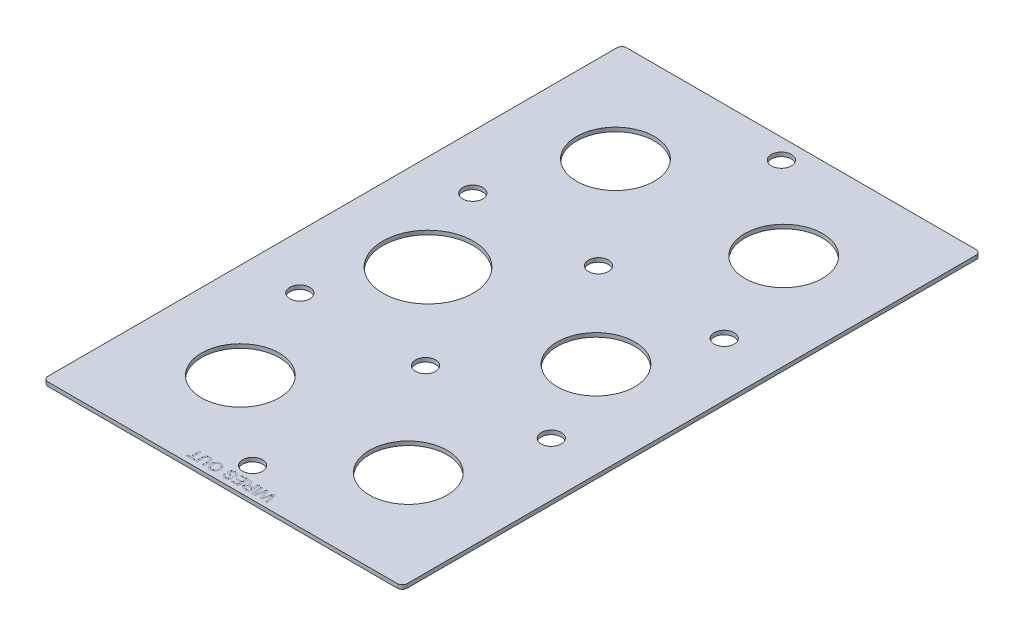
SolidWorks part; units mm, degrees
ref_plane "Front" through (0, 0, 0) normal (0, 0, 1) x (1, 0, 0)
ref_plane "Top" through (0, 0, 0) normal (0, 1, 0) x (1, 0, 0)
ref_plane "Right" through (0, 0, 0) normal (1, 0, 0) x (0, 0, -1)
sketch "Sketch1" plane through (0, 0, 0) normal (0, 1, 0) x (1, 0, 0)
  line L0 (-78.1178, -119.38) -> (-78.2448, -119.38) construction
  line L1 (-111.125, 184.15) -> (111.125, 184.15)
  line L2 (-114.3, 180.975) -> (-114.3, -180.975)
  line L3 (-111.125, -184.15) -> (111.125, -184.15)
  line L4 (114.3, 180.975) -> (114.3, -180.975)
  line L5 (-114.3, 184.15) -> (114.3, -184.15) construction
  line L6 (-114.3, -184.15) -> (114.3, 184.15) construction
  line L7 (-73.1137, 20.0643) -> (-33.9219, -19.9357) construction
  circle A0 centre (53.5178, -119.5086) radius 24.727
  circle A1 centre (53.5178, -0.0643) radius 24.727
  circle A2 centre (-53.5178, -119.38) radius 24.727
  circle A4 centre (-53.5178, 119.38) radius 24.727
  circle A5 centre (53.5178, 119.38) radius 24.727
  arc A6 (-29.1293, -122.5989) -> (-75.7712, -108.8944) centre (-53.5178, -119.38) ccw construction
  arc A7 (-29.1293, -122.5989) -> (-77.9063, -116.1611) centre (-53.5178, -119.38) ccw construction
  arc A8 (114.3, 180.975) -> (111.125, 184.15) centre (111.125, 180.975) ccw
  arc A9 (-114.3, 180.975) -> (-111.125, 184.15) centre (-111.125, 180.975) cw
  arc A10 (-114.3, -180.975) -> (-111.125, -184.15) centre (-111.125, -180.975) ccw
  arc A11 (111.125, -184.15) -> (114.3, -180.975) centre (111.125, -180.975) ccw
  circle A12 centre (-53.5178, 0.0643) radius 28.7693
  circle A13 centre (-80.01, -55.0291) radius 2.2479 construction
  circle A14 centre (-80.01, -55.0291) radius 2.2479 construction
  circle A15 centre (0, -55.0333) radius 2.2479 construction
  circle A16 centre (0, -55.0333) radius 2.2479 construction
  circle A17 centre (80.01, -55.0291) radius 2.2479 construction
  circle A18 centre (80.01, -55.0291) radius 2.2479 construction
  circle A19 centre (80.01, 55.0291) radius 2.2479 construction
  circle A20 centre (80.01, 55.0291) radius 2.2479 construction
  circle A21 centre (0, 55.0333) radius 2.2479 construction
  circle A22 centre (0, 55.0333) radius 2.2479 construction
  circle A23 centre (-80.01, 55.0291) radius 2.2479 construction
  circle A24 centre (-80.01, 55.0291) radius 2.2479 construction
  circle A25 centre (0, 171.45) radius 2.2479 construction
  circle A26 centre (0, 171.45) radius 2.2479 construction
  circle A27 centre (0, -165.1) radius 2.2479 construction
  circle A28 centre (0, -165.1) radius 2.2479 construction
  circle A29 centre (0, -165.1) radius 6.35
  circle A30 centre (80.01, -55.0291) radius 6.35
  circle A31 centre (0, -55.0333) radius 6.35
  circle A32 centre (-80.01, -55.0291) radius 6.35
  circle A33 centre (80.01, 55.0291) radius 6.35
  circle A34 centre (0, 55.0333) radius 6.35
  circle A35 centre (-80.01, 55.0291) radius 6.35
  circle A36 centre (0, 171.45) radius 6.35
  point P0 (0, 0)
  dimension "D3" = 0.127
  dimension "D4" = 3.175
  dimension "D5" = 12.7
  dimension "D1" = 228.6
  dimension "D2" = 368.3
extrude "Boss-Extrude1" add sketch "Sketch1" along normal blind 2.54
sketch "Sketch2" plane through (0, 2.54, 0) normal (0, 1, 0) x (1, 0, 0)
  line L0 (0, -184.15) -> (0, -174.15) construction
  line L1 (-111.125, -184.15) -> (111.125, -184.15) construction
  line L2 (25.4, -174.15) -> (-25.4, -174.15) construction
  text T0 "WIRES OUT" font "Arial" height in points 26
  point P7 (0, -174.15)
  dimension "D1" = 10
  dimension "D2" = 50.8
extrude "Cut-Extrude2" cut sketch "Sketch2" against normal blind 0.0254
